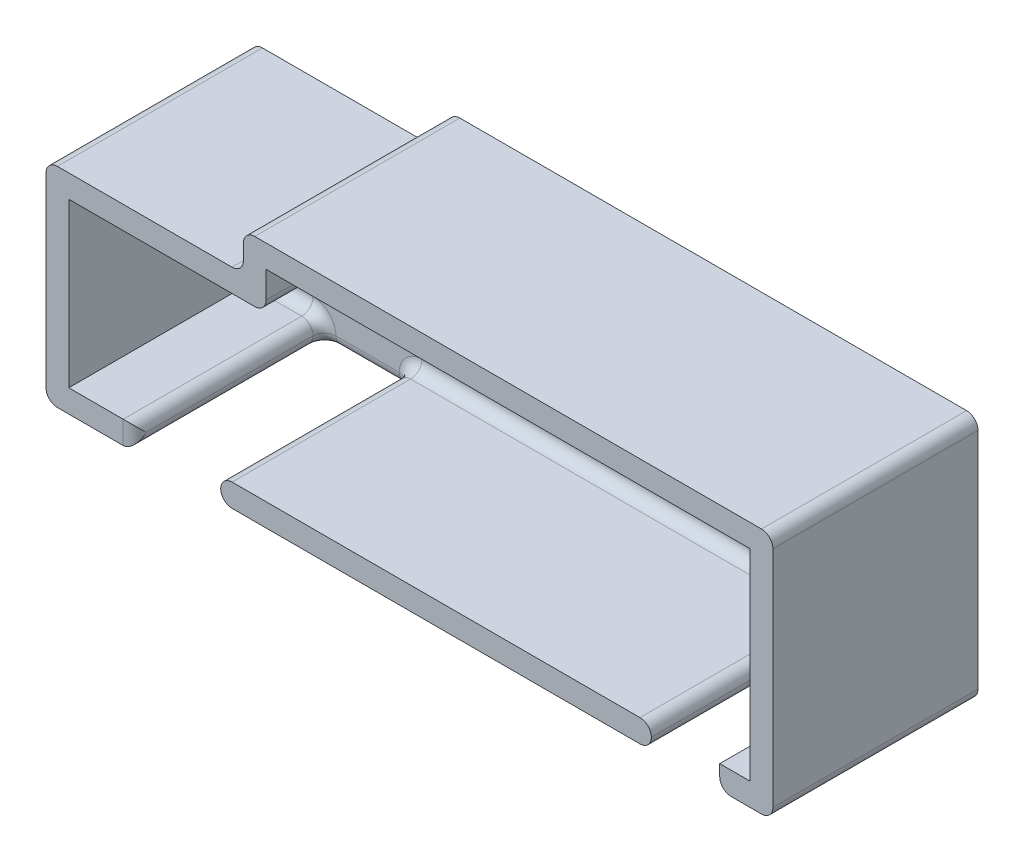
SolidWorks part; units mm, degrees
material "ABS"
ref_plane "X-Y Datum" through (0, 0, 0) normal (0, 0, 1) x (1, 0, 0)
ref_plane "X-Z Datum" through (0, 0, 0) normal (0, 1, 0) x (1, 0, 0)
ref_plane "Y-Z Datum" through (0, 0, 0) normal (1, 0, 0) x (0, 0, -1)
sketch "Sketch1" plane through (0, 0, -724.1914) normal (0, 0, 1) x (1, 0, 0)
  line L1 (476.4614, 467.0983) -> (476.4614, 412.0983)
  line L3 (476.4614, 412.0983) -> (285.0631, 412.0983)
  line L6 (285.0631, 467.0983) -> (285.0631, 412.0983)
  line L8 (285.0631, 467.0983) -> (337.0306, 467.0983)
  line L11 (476.4614, 467.0983) -> (476.4614, 477.0983)
  line L12 (476.4614, 477.0983) -> (337.0306, 477.0983)
  line L13 (337.0306, 467.0983) -> (337.0306, 477.0983)
  dimension "D1" = 191.3983
  dimension "D2" = 55
  dimension "D3" = 10
  dimension "D4" = 139.4307
  dimension "D5" = 191.3983
  dimension "D6" = 51.9675
extrude "Boss-Extrude1" add sketch "Sketch1" along normal blind 4
sketch "Sketch2" plane through (0, 0, -720.1914) normal (0, 0, 1) x (1, 0, 0)
  line L18 (343.0306, 461.0983) -> (291.0631, 461.0983)
  line L19 (291.0631, 461.0983) -> (291.0631, 418.0983)
  line L20 (291.0631, 418.0983) -> (470.4614, 418.0983)
  line L21 (470.4614, 418.0983) -> (470.4614, 471.0983)
  line L22 (343.0306, 461.0983) -> (291.0631, 461.0983)
  line L23 (291.0631, 461.0983) -> (291.0631, 418.0983)
  line L24 (291.0631, 418.0983) -> (470.4614, 418.0983)
  line L25 (470.4614, 418.0983) -> (470.4614, 471.0983)
  line L46 (343.0306, 471.0983) -> (343.0306, 461.0983)
  line L47 (343.0306, 471.0983) -> (343.0306, 461.0983)
  line L48 (470.4614, 471.0983) -> (343.0306, 471.0983)
  line L49 (470.4614, 471.0983) -> (343.0306, 471.0983)
  dimension "D1" = 6
extrude "Boss-Extrude2" add sketch "Sketch2" along normal blind 50
sketch "Sketch3" plane through (0, 0, -670.1914) normal (0, 0, 1) x (1, 0, 0)
  line L0 (291.0631, 418.0983) -> (470.4614, 418.0983) construction
  line L1 (291.0631, 418.0983) -> (470.4614, 418.0983)
  line L11 (470.4614, 418.0983) -> (470.4614, 471.0983) construction
  line L12 (343.0306, 461.0983) -> (291.0631, 461.0983) construction
  line L16 (285.0631, 412.0983) -> (476.4614, 412.0983) construction
  line L17 (308.3954, 418.0983) -> (308.3954, 412.0983)
  line L23 (462.4614, 406.2672) -> (444.4614, 406.2672)
  line L24 (462.4614, 406.2672) -> (462.4614, 427.5833)
  line L25 (462.4614, 427.5833) -> (444.4614, 427.5833)
  line L26 (444.4614, 406.2672) -> (444.4614, 427.5833)
  line L27 (291.0631, 418.0983) -> (331.0631, 418.0983)
  line L28 (291.0631, 418.0983) -> (291.0631, 412.0983)
  line L29 (291.0631, 412.0983) -> (331.0631, 412.0983)
  line L30 (331.0631, 418.0983) -> (331.0631, 412.0983)
  line L32 (476.4614, 477.0983) -> (337.0306, 477.0983)
  line L33 (337.0306, 477.0983) -> (337.0306, 467.0983)
  line L34 (337.0306, 467.0983) -> (285.0631, 467.0983)
  line L35 (285.0631, 467.0983) -> (285.0631, 412.0983)
  line L36 (285.0631, 412.0983) -> (476.4614, 412.0983)
  line L37 (476.4614, 412.0983) -> (476.4614, 477.0983)
  line L38 (476.4614, 477.0983) -> (337.0306, 477.0983)
  line L39 (337.0306, 477.0983) -> (337.0306, 467.0983)
  line L40 (337.0306, 467.0983) -> (285.0631, 467.0983)
  line L41 (285.0631, 467.0983) -> (285.0631, 412.0983)
  line L42 (285.0631, 412.0983) -> (476.4614, 412.0983)
  line L43 (476.4614, 412.0983) -> (476.4614, 477.0983)
  line M39 (285.0631, 412.0983) -> (476.4614, 412.0983)
  dimension "D1" = 8
  dimension "D2" = 40
  dimension "D3" = 18
  dimension "D4" = 21.3161
  dimension "D5" = 33.515
  dimension "D6" = 0
extrude "Cut-Extrude1" cut sketch "Sketch3" against normal up to surface (50 mm away) and the other way through all contours L30 L1 L17 M39 | L26 L24 L1 M39 up to face at (368.185, 450.0983, -720.1914)
fillet "Fillet3" radius 3 26 edges at (343.0306, 461.0983, -695.1914) (337.0306, 477.0983, -697.1914) (337.0306, 467.0983, -697.1914) (285.0631, 467.0983, -697.1914) (476.4614, 477.0983, -697.1914) (476.4614, 412.0983, -697.1914) (285.0631, 412.0983, -697.1914) (453.4614, 412.0983, -720.1914) (319.7292, 412.0983, -720.1914) (343.0306, 466.0983, -720.1914) (331.0631, 418.0983, -695.1914) (444.4614, 418.0983, -695.1914) (462.4614, 415.0983, -720.1914) (387.7622, 418.0983, -720.1914) (466.4614, 418.0983, -720.1914) (470.4614, 444.5983, -720.1914) (406.746, 471.0983, -720.1914) (317.0469, 461.0983, -720.1914) (331.0631, 412.0983, -695.1914) (462.4614, 412.0983, -695.1914) (444.4614, 412.0983, -695.1914) (299.7292, 418.0983, -720.1914) (308.3954, 418.0983, -695.1914) (308.3954, 412.0983, -695.1914) (308.3954, 415.0983, -670.1914) (308.3954, 415.0983, -720.1914)
